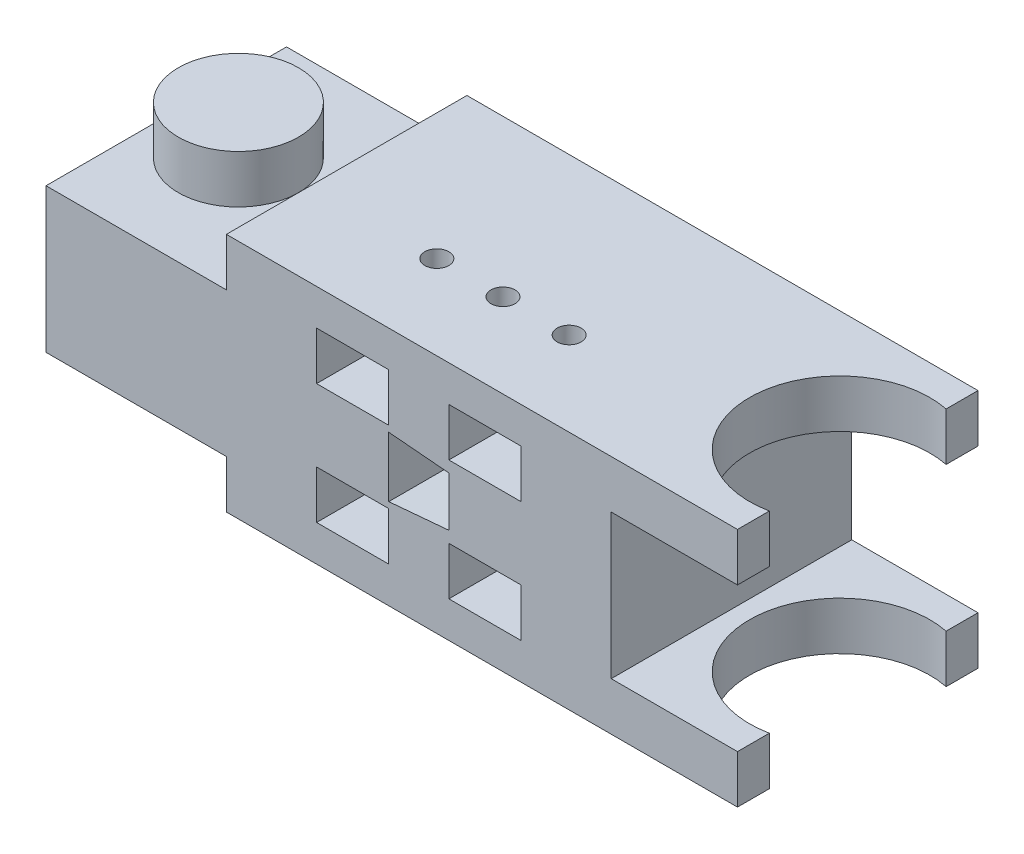
SolidWorks part; units mm, degrees
ref_plane "Front Plane" through (0, 0, 0) normal (0, 0, 1) x (1, 0, 0)
ref_plane "Top Plane" through (0, 0, 0) normal (0, 1, 0) x (1, 0, 0)
ref_plane "Right Plane" through (0, 0, 0) normal (1, 0, 0) x (0, 0, -1)
sketch "Sketch1" plane through (0, 0, 0) normal (0, 0, 1) x (1, 0, 0)
  line L0 (0, 0) -> (-19.5, 0) construction
  line L5 (-19.5, 0) -> (-30.5, 0) construction
  line L6 (-30.5, 0) -> (-50, 0) construction
  line L7 (-50, -6) -> (-42.5, -6) construction
  line L8 (-50, -10) -> (0, -10) construction
  line L9 (-50, -10) -> (-50, 10) construction
  line L10 (-50, 10) -> (0, 10) construction
  line L11 (0, -10) -> (0, 10) construction
  line L12 (-50, -10) -> (0, 10) construction
  line L13 (-50, 10) -> (0, -10) construction
  line L14 (-41, -10) -> (-41, -6)
  line L15 (-41, -6) -> (-50, -6)
  line L16 (-41, 10) -> (-41, 6)
  line L17 (-41, 6) -> (-50, 6)
  line L18 (-50, 6) -> (-56, 6)
  line L19 (-56, 6) -> (-56, -6)
  line L20 (-56, -6) -> (-50, -6)
  line L21 (-41, 10) -> (0, 10) construction
  line L22 (-41, -10) -> (0, -10)
  line L23 (0, 10) -> (1.5, 10)
  line L24 (1.5, 10) -> (1.5, 6)
  line L25 (1.5, 6) -> (0, 6)
  line L26 (0, -10) -> (1.5, -10)
  line L27 (1.5, -10) -> (1.5, -6)
  line L28 (1.5, -6) -> (0, -6)
  line L29 (0, 6) -> (0, -6) construction
  line L30 (0, 6) -> (-9, 6)
  line L31 (-9, 6) -> (-9, -6)
  line L32 (-9, -6) -> (0, -6)
  line L33 (-7.5, 0) -> (0, 0) construction
  line L34 (-7.5, 0) -> (-9, 0) construction
  line L35 (-41, 10) -> (0, 10)
  line L36 (0, 0) -> (1.5, 0) construction
  line L37 (1.5, 0) -> (1.5, 6) construction
  line L38 (-42.5, -6) -> (-41, -6) construction
  point P2 (-25, 0)
  point P26 (3.6042, 0)
  dimension "D2" = 19.5
  dimension "D3" = 11
  dimension "D4" = 19.5
  dimension "D6" = 20
  dimension "D7" = 4
  dimension "D8" = 4
  dimension "D1" = 7.5
  dimension "D9" = 1.5
  dimension "D10" = 6
  dimension "D5" = 7.5
  dimension "D11" = 1.5
  dimension "D12" = 1.5
extrude "Boss-Extrude1" add sketch "Sketch1" along normal blind 20
sketch "Sketch2" plane through (0, -6, 0) normal (0, -1, 0) x (1, 0, 0)
  line L0 (-50, 0) -> (0, 0) construction
  line L1 (-50, 0) -> (0, 0) construction
  line L2 (-50, 0) -> (-50, 20) construction
  line L3 (-56, 20) -> (-41, 20) construction
  circle A0 centre (-50, 10) radius 5
  dimension "D1" = 10
extrude "Boss-Extrude2" add sketch "Sketch2" along normal blind 4
sketch "Sketch3" plane through (0, -10, 0) normal (0, -1, 0) x (1, 0, 0)
  line L0 (0, 0) -> (0, 20) construction
  line L1 (-41, 20) -> (1.5, 20) construction
  circle A0 centre (0, 10) radius 7.5
  dimension "D1" = 15
extrude "Cut-Extrude1" cut sketch "Sketch3" against normal up to surface (20 mm away) up to face at (-19.75, 10, 10)
mirror "Mirror1" about plane through (0, 0, 0) normal (0, 1, 0) of "Boss-Extrude2"
sketch "Sketch4" plane through (0, 0, 20) normal (0, 0, 1) x (1, 0, 0)
  line L0 (0, -10) -> (0, 10) construction
  line L1 (0, -10) -> (0, 10) construction
  line L2 (0, 0) -> (-25, 0) construction
  line L3 (-19.5, 0) -> (-30.5, 0) construction
  line L4 (-27.5, 2.5) -> (-22.5, 2.0626)
  line L5 (-27.5, -2.5) -> (-22.5, -2.5) construction
  line L6 (-27.5, -2.5) -> (-27.5, 2.5)
  line L7 (-27.5, 2.5) -> (-22.5, 2.5) construction
  line L8 (-22.5, -2.5) -> (-22.5, 2.5) construction
  line L9 (-27.5, -2.5) -> (-22.5, 2.5) construction
  line L10 (-27.5, 2.5) -> (-22.5, -2.5) construction
  line L11 (-27.5, -2.5) -> (-22.5, -2.0626)
  line L12 (-22.5, 2.0626) -> (-22.5, -2.0626)
  point P10 (-13.5935, -2.3872)
  point P13 (-22.7742, 0)
  point P14 (-22.6104, -3.5819)
  dimension "D1" = 5
  dimension "D2" = 5
  dimension "D3" = 25
  dimension "D4" = 5
  dimension "D5" = 5
extrude "Cut-Extrude2" cut sketch "Sketch4" against normal blind 10
sketch "Sketch5" plane through (0, 0, 20) normal (0, 0, 1) x (1, 0, 0)
  line L0 (-30.5, 0) -> (-50, 0) construction
  line L1 (-19.5, 0) -> (-30.5, 0) construction
  line L2 (0, 0) -> (-19.5, 0) construction
  line L3 (-30.5, 0) -> (-50, 0) construction
  line L4 (-19.5, 0) -> (-30.5, 0) construction
  line L5 (0, 0) -> (-19.5, 0) construction
  line L6 (-30.5, -5) -> (-30.5, 5) construction
  line L7 (-19.5, -5) -> (-19.5, 5) construction
  line L9 (-33.5, 7) -> (-27.5, 7)
  line L10 (-33.5, 7) -> (-33.5, 3)
  line L11 (-33.5, 3) -> (-27.5, 3)
  line L12 (-27.5, 7) -> (-27.5, 3)
  line L13 (-33.5, 7) -> (-27.5, 3) construction
  line L14 (-33.5, 3) -> (-27.5, 7) construction
  line L15 (-22.5, 7) -> (-16.5, 7)
  line L16 (-22.5, 7) -> (-22.5, 3)
  line L17 (-22.5, 3) -> (-16.5, 3)
  line L18 (-16.5, 7) -> (-16.5, 3)
  line L19 (-22.5, 7) -> (-16.5, 3) construction
  line L20 (-22.5, 3) -> (-16.5, 7) construction
  line L21 (-22.5, -7) -> (-16.5, -7)
  line L22 (-22.5, -7) -> (-22.5, -3)
  line L23 (-22.5, -3) -> (-16.5, -3)
  line L24 (-16.5, -7) -> (-16.5, -3)
  line L25 (-22.5, -7) -> (-16.5, -3) construction
  line L26 (-22.5, -3) -> (-16.5, -7) construction
  line L27 (-33.5, -7) -> (-27.5, -7)
  line L28 (-33.5, -7) -> (-33.5, -3)
  line L29 (-33.5, -3) -> (-27.5, -3)
  line L30 (-27.5, -7) -> (-27.5, -3)
  line L31 (-33.5, -7) -> (-27.5, -3) construction
  line L32 (-33.5, -3) -> (-27.5, -7) construction
  point P7 (-30.5, 0)
  point P10 (-19.5, 0)
  dimension "D1" = 4
  dimension "D2" = 6
  dimension "D3" = 6
extrude "Cut-Extrude3" cut sketch "Sketch5" against normal blind 10
sketch "Sketch6" plane through (0, -10, 0) normal (0, -1, 0) x (1, 0, 0)
  line L0 (-22.5, 10) -> (-16.5, 10) construction
  line L1 (-27.5, 10) -> (-22.5, 10) construction
  line L2 (-33.5, 10) -> (-27.5, 10) construction
  line L3 (-22.5, 10) -> (-16.5, 10) construction
  line L4 (-27.5, 10) -> (-22.5, 10) construction
  line L5 (-33.5, 10) -> (-27.5, 10) construction
  line L6 (-30.5, 10) -> (-30.5, 13) construction
  line L7 (-25, 10) -> (-25, 13) construction
  line L8 (-19.5, 10) -> (-19.5, 13) construction
  circle A0 centre (-30.5, 13) radius 1
  circle A1 centre (-25, 13) radius 1
  circle A2 centre (-19.5, 13) radius 1
  dimension "D1" = 3
extrude "Cut-Extrude4" cut sketch "Sketch6" against normal up to surface (20 mm away) up to face at (-14.1667, 10, 10)
equation "\"offset\"=5"
equation "\"x_0\" = 19.5"
equation "\"D2@Sketch1\"=\"x_0\""
equation "\"x_1\" = 11"
equation "\"D3@Sketch1\"=\"x_1\""
equation "\"x_2\"= 19.5"
equation "\"D4@Sketch1\"=\"x_2\""
equation "\"bearing_width\" = 4"
equation "\"link_width\" = 20"
equation "\"link_height\" = 20"
equation "\"D6@Sketch1\"=\"link_width\""
equation "\"D7@Sketch1\"=\"bearing_width\""
equation "\"D8@Sketch1\"=\"bearing_width\""
equation "\"D1@Boss-Extrude1\"=\"link_height\""
equation "\"D1@Boss-Extrude2\"=\"bearing_width\""
equation "\"bearing_OD\" = 15"
equation "\"bearing_ID\"= 10"
equation "\"D1@Sketch3\"=\"bearing_OD\""
equation "\"D1@Sketch1\"=\"bearing_OD\"/2"
equation "\"bearing_offset\"= 1.5"
equation "\"D9@Sketch1\"=\"bearing_offset\""
equation "\"bearing_backstop_offset\"=6"
equation "\"D10@Sketch1\"=\"bearing_backstop_offset\""
equation "\"D5@Sketch1\"=\"bearing_OD\"/2"
equation "\"D11@Sketch1\"=\"bearing_offset\""
equation "\"D12@Sketch1\"=\"bearing_offset\""
equation "\"chuck_width\" = 5"
equation "\"D4@Sketch4\"=\"chuck_width\""
equation "\"chuck_angle\"=5"
equation "\"D2@Sketch4\"=\"chuck_angle\""
equation "\"D1@Sketch4\"=\"chuck_angle\""
equation "\"chuck_length\" = 5"
equation "\"chuck_depth\" = 10"
equation "\"D1@Cut-Extrude2\"=\"chuck_depth\""
equation "\"D5@Sketch4\"=\"chuck_length\""
equation "\"chuck_distance\"=25"
equation "\"D3@Sketch4\"=\"chuck_distance\""
equation "\"post_width\" = 4"
equation "\"D1@Sketch5\"=\"post_width\""
equation "\"post_length\"=6"
equation "\"D2@Sketch5\"=\"post_length\""
equation "\"post_bearing_width\"= 6"
equation "\"D3@Sketch5\"=\"post_bearing_width\""
equation "\"post_depth\"=10"
equation "\"D1@Cut-Extrude3\"=\"post_depth\""
equation "\"pin_offset\" = 3"
equation "\"D1@Sketch6\"=\"pin_offset\""
equation "\"pin_dia\"=2"
equation "\"D2@Sketch6\"=\"pin_dia\""
equation "\"D1@Sketch2\"=\"bearing_ID\""
